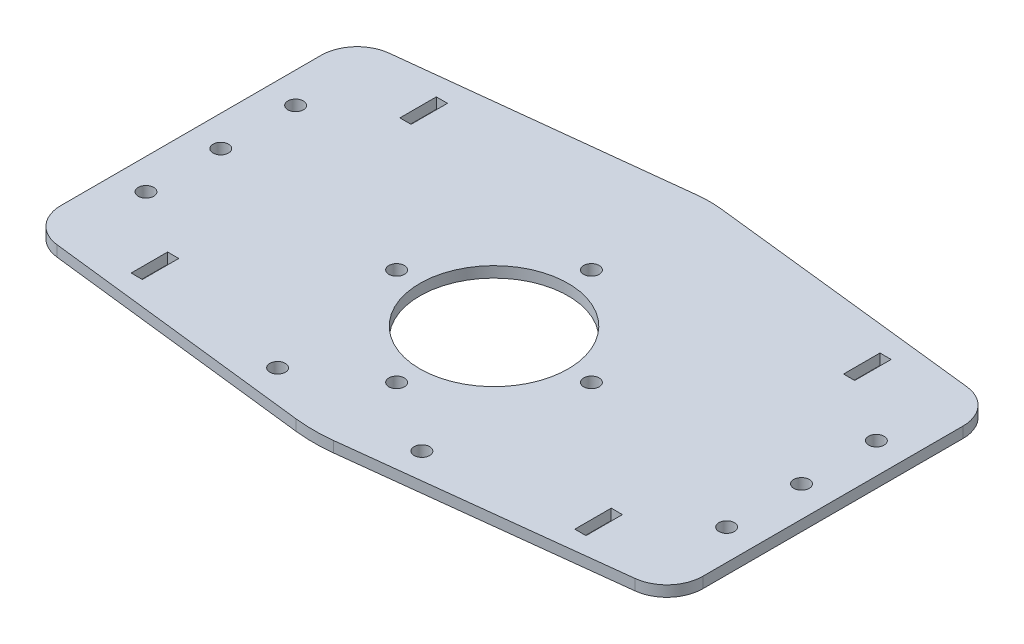
SolidWorks part; units mm, degrees
note: The reader was unsure of these and kept them because the rebuilt part matched: thickness of "Base-Flange1", "Sheet-Metal8", "Sheet-Metal9".
material "3.3549 (EN-AW 5182)"
ref_plane "Front Plane" through (0, 0, 0) normal (0, 0, 1) x (1, 0, 0)
ref_plane "Top Plane" through (0, 0, 0) normal (0, 1, 0) x (1, 0, 0)
ref_plane "Right Plane" through (0, 0, 0) normal (1, 0, 0) x (0, 0, -1)
sketch "Sketch1" plane through (0, 0, 0) normal (0, 1, 0) x (1, 0, 0)
  line L0 (0, -44.7868) -> (0, 44.7868) construction
  line L2 (-89, -40) -> (-89, 50)
  line L3 (-89, 50) -> (89, 50) construction
  line L4 (89, -40) -> (89, 50)
  line L5 (-44.2539, 0) -> (44.2539, 0) construction
  line L8 (-89, -40) -> (-5.1735, -49.7016)
  line L9 (89, -40) -> (5.1735, -49.7016)
  line L10 (-89, 50) -> (-3.3497, 59.6236)
  line L11 (-63.05, 47.05) -> (-59.95, 47.05)
  line L12 (-63.05, 47.05) -> (-63.05, 36.95)
  line L13 (-63.05, 36.95) -> (-59.95, 36.95)
  line L14 (-59.95, 47.05) -> (-59.95, 36.95)
  line L15 (-63.05, 47.05) -> (-59.95, 36.95) construction
  line L16 (-63.05, 36.95) -> (-59.95, 47.05) construction
  line L17 (-63.05, -37.55) -> (-59.95, -37.55)
  line L18 (-63.05, -37.55) -> (-63.05, -27.45)
  line L19 (-63.05, -27.45) -> (-59.95, -27.45)
  line L20 (-59.95, -37.55) -> (-59.95, -27.45)
  line L21 (-63.05, -37.55) -> (-59.95, -27.45) construction
  line L22 (-63.05, -27.45) -> (-59.95, -37.55) construction
  line L23 (3.3497, 59.6236) -> (89, 50)
  line L24 (63.05, -37.55) -> (63.05, -27.45)
  line L25 (63.05, -37.55) -> (59.95, -37.55)
  line L26 (59.95, -37.55) -> (59.95, -27.45)
  line L27 (63.05, -27.45) -> (59.95, -27.45)
  line L28 (63.05, 47.05) -> (59.95, 47.05)
  line L29 (63.05, 47.05) -> (63.05, 36.95)
  line L30 (63.05, 36.95) -> (59.95, 36.95)
  line L31 (59.95, 47.05) -> (59.95, 36.95)
  line L32 (-20, -40) -> (20, -40) construction
  circle A0 centre (0, 0) radius 20.55
  circle A1 centre (0, 27) radius 1
  circle A7 centre (-80.5, 25.5) radius 1
  circle A8 centre (-80.5, 4.75) radius 1
  circle A9 centre (-80.5, -16) radius 1
  circle A10 centre (80.5, -16) radius 1
  circle A11 centre (80.5, 4.75) radius 1
  circle A12 centre (80.5, 25.5) radius 1
  arc A14 (-5.1735, -49.7016) -> (5.1735, -49.7016) centre (0, -5) ccw
  circle A17 centre (27, 0) radius 1
  circle A18 centre (0, -27) radius 1
  circle A19 centre (-27, 0) radius 1
  arc A20 (3.3497, 59.6236) -> (-3.3497, 59.6236) centre (0, 29.8112) ccw
  circle A21 centre (20, -40) radius 1
  circle A22 centre (-20, -40) radius 1
  point P0 (0, 0)
  point P15 (-61.5, 42)
  point P24 (0, 0)
  point P25 (0, 0)
  point P26 (0, 50)
  point P49 (-61.5, -32.5)
  point P58 (0, 60)
  dimension "D3" = 41.1
  dimension "D4" = 2
  dimension "D5" = 27
  dimension "D7" = 80.5
  dimension "D8" = 2
  dimension "D12" = 40
  dimension "D15" = 45
  dimension "D16" = 2
  dimension "D17" = 40
  dimension "D25" = 30
  dimension "D2" = 178
  dimension "D9" = 24.5
  dimension "D10" = 41.5
  dimension "D11" = 20.75
  dimension "D13" = 50
  dimension "D14" = 5
  dimension "D18" = 10.1
  dimension "D19" = 10.1
  dimension "D20" = 74.5
  dimension "D21" = 3.1
  dimension "D22" = 61.5
  dimension "D23" = 3.1
  dimension "D24" = 42
  dimension "D26" = 10
  dimension "D27" = 20
  dimension "D28" = 40
  dimension "D6" = 4
base flange "Base-Flange1" sketch "Sketch1" thickness 3 reverse thickness direction no parameters "D1"=4
fillet "Fillet1" radius 10 4 edges at (89, -1.5, 40) (-89, -1.5, 40) (89, -1.5, -50) (-89, -1.5, -50)
sketch "Sketch4" plane through (0, 0, 0) normal (0, 1, 0) x (1, 0, 0)
  point P0 (-27, 0)
  point P3 (0, 27)
  point P6 (27, 0)
  point P9 (0, -27)
  point P12 (20, -40)
  point P15 (-20, -40)
  point P18 (80.5, -16)
  point P21 (80.5, 25.5)
  point P24 (80.5, 4.75)
  point P27 (-80.5, 25.5)
  point P30 (-80.5, 4.75)
  point P33 (-80.5, -16)
hole_wizard "M4 Clearance Hole2" positions "Sketch4" profile "Sketch3" hole size "M4" standard "ANSI Metric"
sketch "Sketch3" plane through (-27, 0, 0) normal (1, 0, 0) x (0, 0, 1)
  line L0 (0, 0) -> (0, 137.2919)
  line L1 (0, 137.2919) -> (2.15, 136)
  line L2 (2.15, 136) -> (2.15, 0)
  line L5 (2.15, 0) -> (0, 0)
  line L10 (0, 137.2919) -> (-2.15, 136) construction
  line L11 (0, -6.35) -> (0, 107.95) construction
  dimension "Hole Dia." = 4.3
  dimension "Hole Depth" = 136
  dimension "Drill Angle" = 118
sketch "Bend-Lines1" [suppressed] plane through (0, 0, 0) normal (0, 1, 0) x (1, 0, 0)
sketch "Bounding-Box1" [suppressed] plane through (0, 0, 0) normal (0, 1, 0) x (1, 0, 0)
sheet metal parameters "Sheet-Metal8" thickness 3 parameters "D1"=4, "D7"=4
flat pattern "Flat-Pattern8" [suppressed]
sketch "Bend-Lines2" plane through (0, 0, 0) normal (0, 1, 0) x (1, 0, 0)
sketch3d "Bounding-Box2" [suppressed]
  line L0 (87.5, -45, 0) -> (-87.5, -45, 0) construction
  line L1 (87.5, 64.8047, 0) -> (-87.5, 64.8047, 0) construction
  line L2 (87.5, -45, 0) -> (87.5, 64.8047, 0) construction
  line L3 (-87.5, -45, 0) -> (-87.5, 64.8047, 0) construction
sheet metal parameters "Sheet-Metal9" thickness 3 parameters "D1"=4, "D7"=4
flat pattern "Flat-Pattern8"
sketch "Bend-Lines2" plane through (0, 0, 0) normal (0, 1, 0) x (1, 0, 0)
sketch3d "Bounding-Box2" [suppressed]
  line L0 (89, -45, 0) -> (-89, -45, 0) construction
  line L1 (89, 64.8112, 0) -> (-89, 64.8112, 0) construction
  line L2 (89, -45, 0) -> (89, 64.8112, 0) construction
  line L3 (-89, -45, 0) -> (-89, 64.8112, 0) construction
